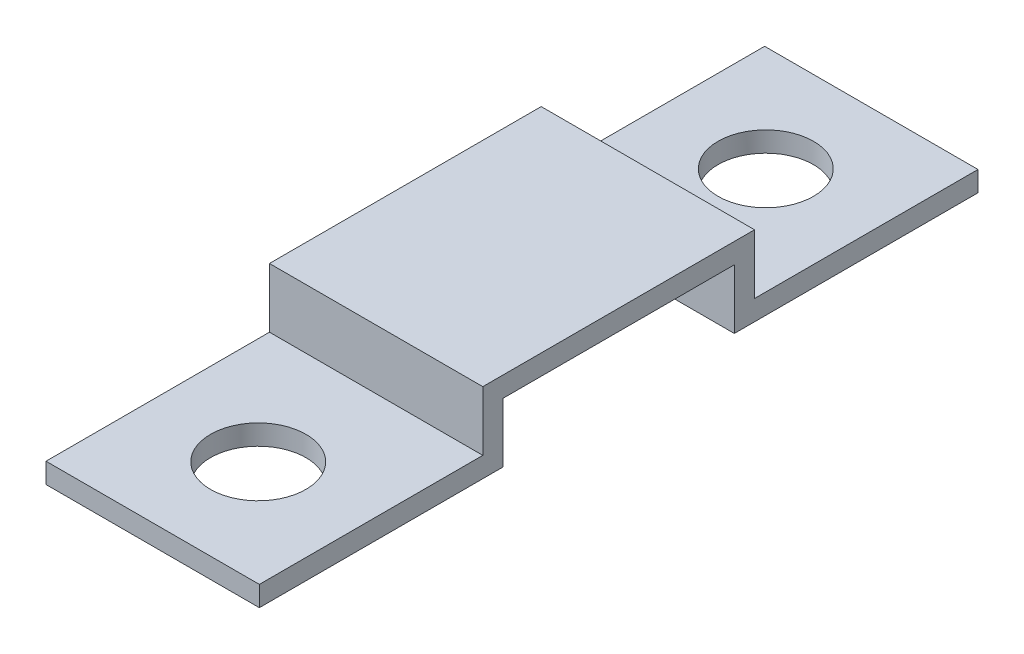
SolidWorks part; units mm, degrees
material "AISI 304"
ref_plane "前视基准面" through (0, 0, 0) normal (0, 0, 1) x (1, 0, 0)
ref_plane "上视基准面" through (0, 0, 0) normal (0, 1, 0) x (1, 0, 0)
ref_plane "右视基准面" through (0, 0, 0) normal (1, 0, 0) x (0, 0, -1)
other "Configuration Table"
sketch "草图5" plane through (0, 0, 0) normal (1, 0, 0) x (0, 0, -1)
  line L0 (0, 0) -> (0, 17100.1177) construction
  line L1 (12.1, 0) -> (-12.1, 0)
  line L2 (-12.1, 0) -> (-12.1, -5.3)
  line L3 (-12.1, -5.3) -> (-32, -5.3)
  line L4 (-32, -5.3) -> (-32, -7.1)
  line L5 (-32, -7.1) -> (-10.3, -7.1)
  line L6 (-10.3, -7.1) -> (-10.3, -1.8)
  line L7 (-10.3, -1.8) -> (10.3, -1.8)
  line L8 (10.3, -7.1) -> (10.3, -1.8)
  line L9 (32, -7.1) -> (10.3, -7.1)
  line L10 (32, -5.3) -> (32, -7.1)
  line L11 (12.1, -5.3) -> (32, -5.3)
  line L12 (12.1, 0) -> (12.1, -5.3)
  point P12 (0, -1.8)
  point P17 (0, 0)
  dimension "D1" = 1.8
  dimension "D2" = 1.8
  dimension "D3" = 1.8
  dimension "D4" = 7.1
  dimension "D5" = 20.6
  dimension "D6" = 64
extrude "凸台-拉伸5" add sketch "草图5" along normal blind 19
sketch "草图6" plane through (0, -5.3, 0) normal (0, 1, 0) x (1, 0, 0)
  line L0 (9.5, -32) -> (9.5, 32) construction
  line L1 (19, -32) -> (0, -32) construction
  line L2 (19, 32) -> (0, 32) construction
  line L3 (0, 0) -> (19, 0) construction
  line L4 (19, 12.1) -> (19, -12.1) construction
  circle A0 centre (9.5, -22.6) radius 4.25
  circle A1 centre (9.5, 22.6) radius 4.25
  dimension "D1" = 8.5
  dimension "D2" = 45.2
extrude "切除-拉伸1" cut sketch "草图6" against normal blind 19
